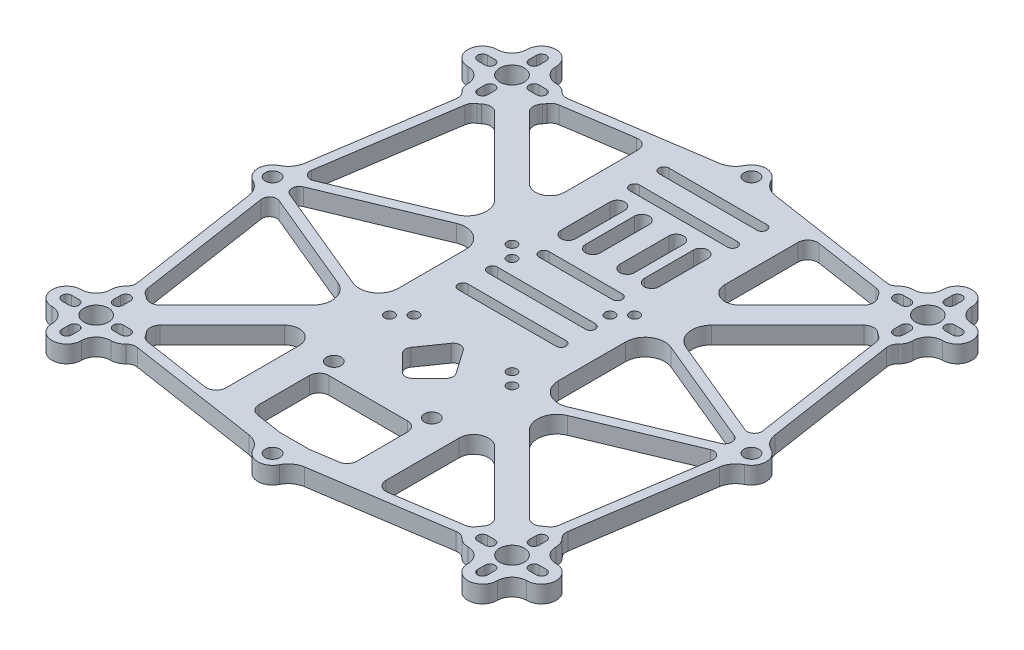
SolidWorks part; units mm, degrees
ref_plane "前视基准面" through (0, 0, 0) normal (0, 0, 1) x (1, 0, 0)
ref_plane "上视基准面" through (0, 0, 0) normal (0, 1, 0) x (1, 0, 0)
ref_plane "右视基准面" through (0, 0, 0) normal (1, 0, 0) x (0, 0, -1)
sketch "草图1" plane through (0, 0, 0) normal (0, 1, 0) x (1, 0, 0)
  line L4 (42.4264, 36.4264) -> (42.4264, 37.9264) construction
  line L5 (41.4264, 36.4264) -> (41.4264, 37.9264)
  line L10 (43.4264, 36.4264) -> (43.4264, 37.9264)
  line L13 (42.4264, 36.4264) -> (42.4264, 37.9264) construction
  line L24 (45.4264, 36.4264) -> (45.4264, 39.4264)
  line L27 (16.3284, 12.8504) -> (16.3284, -12.8504)
  line L28 (48.4264, 42.4264) -> (46.9264, 42.4264) construction
  line L31 (48.4264, 39.4264) -> (45.4264, 39.4264)
  line L33 (48.4264, 45.4264) -> (45.4264, 45.4264)
  line L34 (48.4264, 42.4264) -> (46.9264, 42.4264) construction
  line L35 (48.4264, 43.4264) -> (46.9264, 43.4264)
  line L44 (48.4264, 41.4264) -> (46.9264, 41.4264)
  line L45 (42.4264, 48.4264) -> (42.4264, 46.9264) construction
  line L48 (36.4264, 42.4264) -> (37.9264, 42.4264) construction
  line L51 (45.4264, 48.4264) -> (45.4264, 45.4264)
  line L54 (39.4264, 48.4264) -> (39.4264, 45.4264)
  line L57 (36.4264, 45.4264) -> (39.4264, 45.4264)
  line L59 (42.4264, 48.4264) -> (42.4264, 46.9264) construction
  line L62 (43.4264, 48.4264) -> (43.4264, 46.9264)
  line L63 (41.4264, 48.4264) -> (41.4264, 46.9264)
  line L64 (36.4264, 42.4264) -> (37.9264, 42.4264) construction
  line L65 (36.4264, 41.4264) -> (37.9264, 41.4264)
  line L66 (36.4264, 43.4264) -> (37.9264, 43.4264)
  line L67 (16.3284, 44.3567) -> (33.5024, 41.7553)
  line L68 (0, 42) -> (10, 42)
  line L69 (0, 40) -> (10, 40)
  line L70 (0, 1) -> (0, 5)
  line L71 (0, 1) -> (10, 1)
  line L72 (0, -1) -> (10, -1)
  line L73 (-1, 0) -> (-4.9453, 0)
  line L77 (7.5, 13) -> (0, 13)
  line L78 (48.4035, 2.9662) -> (43.7435, 33.731)
  line L85 (36.4264, -42.4264) -> (37.9264, -42.4264) construction
  line L87 (42.4264, -48.4264) -> (42.4264, -46.9264) construction
  line L88 (48.4264, -42.4264) -> (46.9264, -42.4264) construction
  line L89 (42.4264, -36.4264) -> (42.4264, -37.9264) construction
  line L92 (41.7553, -33.5024) -> (46.4493, -2.5135)
  line L94 (41.7553, 33.5024) -> (46.4493, 2.5135)
  line L95 (16.3284, 19.864) -> (16.3284, 44.3567)
  line L96 (48.4035, -2.9662) -> (43.7435, -33.731)
  line L99 (36.4264, -45.4264) -> (39.4264, -45.4264)
  line L100 (39.4264, -48.4264) -> (39.4264, -45.4264)
  line L101 (45.4264, -48.4264) -> (45.4264, -45.4264)
  line L102 (48.4264, -45.4264) -> (45.4264, -45.4264)
  line L103 (48.4264, -39.4264) -> (45.4264, -39.4264)
  line L104 (45.4264, -36.4264) -> (45.4264, -39.4264)
  line L107 (36.4264, -42.4264) -> (37.9264, -42.4264) construction
  line L108 (36.4264, -41.4264) -> (37.9264, -41.4264)
  line L109 (36.4264, -43.4264) -> (37.9264, -43.4264)
  line L110 (42.4264, -48.4264) -> (42.4264, -46.9264) construction
  line L111 (43.4264, -48.4264) -> (43.4264, -46.9264)
  line L112 (41.4264, -48.4264) -> (41.4264, -46.9264)
  line L113 (48.4264, -42.4264) -> (46.9264, -42.4264) construction
  line L114 (48.4264, -43.4264) -> (46.9264, -43.4264)
  line L115 (48.4264, -41.4264) -> (46.9264, -41.4264)
  line L116 (42.4264, -36.4264) -> (42.4264, -37.9264) construction
  line L117 (41.4264, -36.4264) -> (41.4264, -37.9264)
  line L118 (43.4264, -36.4264) -> (43.4264, -37.9264)
  line L119 (33.731, 43.7435) -> (2.9662, 48.4035)
  line L120 (0, 51.8528) -> (0, 50.3528)
  line L125 (0, 47.3528) -> (0, 42)
  line L126 (0, -47.3528) -> (0, -44.4131)
  line L127 (0, -51.8528) -> (0, -50.3528)
  line L128 (33.731, -43.7435) -> (2.9662, -48.4035)
  line L129 (16.3284, -44.3567) -> (33.5024, -41.7553)
  line L130 (16.3284, -19.864) -> (16.3284, -44.3567)
  line L131 (5.3245, -17.0379) -> (0, -22.3624)
  line L133 (0, -29.3528) -> (10, -29.3528)
  line L135 (10, -43.3528) -> (3, -44.4131)
  line L137 (3, -44.4131) -> (0, -44.4131)
  line L138 (10, -29.3528) -> (10, -43.3528)
  line L139 (0, -29.3528) -> (0, -22.3624)
  line L140 (8.5, 30) -> (8.5, 20) construction
  line L141 (10, 30) -> (10, 20)
  line L142 (7, 30) -> (7, 20)
  line L143 (3.5, 30) -> (3.5, 20) construction
  line L144 (5, 30) -> (5, 20)
  line L145 (2, 30) -> (2, 20)
  line L148 (7.5, 15) -> (0, 15)
  line L149 (0, 7) -> (0, 13)
  line L150 (0, -1) -> (0, -9.4338)
  line L152 (5.3245, -17.0379) -> (0, -9.4338)
  line L154 (0, -9.4338) -> (0, -1)
  line L155 (0, 5) -> (10, 5)
  line L156 (0, 7) -> (10, 7)
  line L157 (0, 15) -> (0, 34)
  line L158 (0, 34) -> (10, 34)
  line L159 (0, 36) -> (10, 36)
  line L160 (0, 36) -> (0, 40)
  line L161 (47.2877, 0) -> (16.3284, -12.8504)
  line L162 (47.2877, 0) -> (16.3284, 12.8504)
  line L163 (39.4674, -35.9319) -> (17.8993, -14.3638)
  line L164 (39.4674, 35.9319) -> (17.8993, 14.3638)
  line L165 (17.8993, 14.3638) -> (46.4493, 2.5135)
  line L166 (16.3284, -19.864) -> (35.9319, -39.4674)
  line L167 (17.8993, -14.3638) -> (46.4493, -2.5135)
  line L168 (16.3284, 19.864) -> (35.9319, 39.4674)
  circle A48 centre (10, 10) radius 1
  circle A49 centre (12.5, 12.5) radius 1
  arc A52 (41.4264, 36.4264) -> (43.4264, 36.4264) centre (42.4264, 36.4264) ccw
  arc A53 (43.4264, 37.9264) -> (41.4264, 37.9264) centre (42.4264, 37.9264) ccw
  arc A54 (39.4674, 35.9319) -> (41.7553, 33.5024) centre (42.4264, 36.4264) ccw
  arc A56 (48.4264, 45.4264) -> (48.4264, 39.4264) centre (48.4264, 42.4264) cw
  arc A57 (48.4264, 43.4264) -> (48.4264, 41.4264) centre (48.4264, 42.4264) cw
  arc A58 (46.9264, 41.4264) -> (46.9264, 43.4264) centre (46.9264, 42.4264) cw
  arc A59 (45.4264, 48.4264) -> (39.4264, 48.4264) centre (42.4264, 48.4264) ccw
  arc A61 (43.4264, 48.4264) -> (41.4264, 48.4264) centre (42.4264, 48.4264) ccw
  arc A62 (41.4264, 46.9264) -> (43.4264, 46.9264) centre (42.4264, 46.9264) ccw
  arc A63 (36.4264, 41.4264) -> (36.4264, 43.4264) centre (36.4264, 42.4264) cw
  arc A64 (37.9264, 43.4264) -> (37.9264, 41.4264) centre (37.9264, 42.4264) cw
  circle A65 centre (42.4264, 42.4264) radius 2.5
  arc A69 (10, 40) -> (10, 42) centre (10, 41) ccw
  arc A71 (10, -1) -> (10, 1) centre (10, 0) ccw
  arc A76 (33.5024, 41.7553) -> (35.9319, 39.4674) centre (36.4264, 42.4264) ccw
  arc A77 (33.5024, -43.0975) -> (36.4264, -45.4264) centre (36.4264, -42.4264) ccw
  arc A79 (0, 50.3528) -> (0, 47.3528) centre (0, 48.8528) cw
  arc A80 (2.9662, 48.4035) -> (0, 51.8528) centre (0, 48.8528) ccw
  circle A81 centre (42.4264, -42.4264) radius 2.5
  arc A82 (35.9319, -39.4674) -> (33.731, -41.1093) centre (36.4264, -42.4264) ccw
  arc A83 (45.4264, -48.4264) -> (39.4264, -48.4264) centre (42.4264, -48.4264) cw
  arc A84 (48.4264, -45.4264) -> (48.4264, -39.4264) centre (48.4264, -42.4264) ccw
  arc A85 (39.4674, -35.9319) -> (41.7553, -33.5024) centre (42.4264, -36.4264) cw
  circle A86 centre (12.5, -12.5) radius 1
  circle A87 centre (10, -10) radius 1
  arc A88 (36.4264, -41.4264) -> (36.4264, -43.4264) centre (36.4264, -42.4264) ccw
  arc A89 (37.9264, -43.4264) -> (37.9264, -41.4264) centre (37.9264, -42.4264) ccw
  arc A90 (43.4264, -48.4264) -> (41.4264, -48.4264) centre (42.4264, -48.4264) cw
  arc A91 (41.4264, -46.9264) -> (43.4264, -46.9264) centre (42.4264, -46.9264) cw
  arc A92 (48.4264, -43.4264) -> (48.4264, -41.4264) centre (48.4264, -42.4264) ccw
  arc A93 (46.9264, -41.4264) -> (46.9264, -43.4264) centre (46.9264, -42.4264) ccw
  arc A94 (41.4264, -36.4264) -> (43.4264, -36.4264) centre (42.4264, -36.4264) cw
  arc A95 (43.4264, -37.9264) -> (41.4264, -37.9264) centre (42.4264, -37.9264) cw
  circle A99 centre (48.8528, 0) radius 1.5
  arc A101 (48.4035, -2.9662) -> (48.4035, 2.9662) centre (48.8528, 0) ccw
  arc A102 (43.7435, 33.731) -> (45.4264, 36.4264) centre (42.4264, 36.4264) ccw
  arc A104 (43.7435, -33.731) -> (45.4264, -36.4264) centre (42.4264, -36.4264) cw
  arc A105 (36.4264, 45.4264) -> (33.731, 43.7435) centre (36.4264, 42.4264) ccw
  arc A106 (2.9662, -48.4035) -> (0, -51.8528) centre (0, -48.8528) cw
  arc A107 (0, -50.3528) -> (0, -47.3528) centre (0, -48.8528) ccw
  arc A108 (33.5024, -41.7553) -> (35.9319, -39.4674) centre (36.4264, -42.4264) cw
  circle A109 centre (10, -26.3528) radius 1.5
  arc A110 (10, 30) -> (7, 30) centre (8.5, 30) ccw
  arc A111 (7, 20) -> (10, 20) centre (8.5, 20) ccw
  arc A112 (5, 30) -> (2, 30) centre (3.5, 30) ccw
  arc A113 (2, 20) -> (5, 20) centre (3.5, 20) ccw
  arc A114 (7.5, 13) -> (7.5, 15) centre (7.5, 14) ccw
  arc A115 (10, 5) -> (10, 7) centre (10, 6) ccw
  arc A116 (10, 34) -> (10, 36) centre (10, 35) ccw
  point P0 (8.5, 25)
  point P11 (42.4264, 37.1764)
  point P16 (42.4264, 37.1764)
  point P28 (47.6764, 42.4264)
  point P29 (47.6764, 42.4264)
  point P44 (5, 30)
  point P47 (42.4264, 47.6764)
  point P48 (37.1764, 42.4264)
  point P49 (42.4264, 47.6764)
  point P54 (37.1764, 42.4264)
  point P63 (5, 0)
  point P118 (15.3284, 0)
  point P127 (37.1764, -42.4264)
  point P134 (42.4264, -47.6764)
  point P139 (47.6764, -42.4264)
  point P144 (42.4264, -37.1764)
  point P145 (42.4264, -37.1764)
  point P166 (3.75, 4)
  point P167 (3.5, 25)
extrude "凸台-拉伸1" add sketch "草图1" along normal blind 3.5 contours A107 L127 A106 L128 A77 L99 L100 A83 L101 L102 A84 L103 L104 A104 L96 A101 L78 A102 L24 L31 A56 L33 L51 A59 L54 L57 A105 L119 A80 L120 A79 L125 L68 A69 L69 L71 A71 L72 L139 L133 L138 L135 L137 L126 A113 L145 A112 region at (43.9876, 0, -35.4516)
fillet "圆角1" radius 2 17 edges at (16.3284, 1.75, -44.3567) (16.3284, 1.75, 44.3567) (41.7553, 1.75, 33.5024) (33.5024, 1.75, 41.7553) (43.7435, 1.75, -33.731) (33.731, 1.75, -43.7435) (33.5024, 1.75, -41.7553) (41.7553, 1.75, -33.5024) (33.731, 1.75, 43.7435) (43.7435, 1.75, 33.731) (10, 1.75, 43.3528) (3, 1.75, 44.4131) (10, 1.75, 29.3528) (35.9319, 1.75, -39.4674) (39.4674, 1.75, -35.9319) (35.9319, 1.75, 39.4674) (39.4674, 1.75, 35.9319)
fillet "圆角2" radius 4 8 edges at (2.9662, 1.75, 48.4035) (2.9662, 1.75, -48.4035) (48.4035, 1.75, -2.9662) (48.4035, 1.75, 2.9662) (16.3284, 1.75, 12.8504) (16.3284, 1.75, -12.8504) (17.8993, 1.75, 14.3638) (17.8993, 1.75, -14.3638)
fillet "圆角3" radius 3 8 edges at (39.4264, 1.75, 45.4264) (45.4264, 1.75, 39.4264) (45.4264, 1.75, 45.4264) (39.4264, 1.75, -45.4264) (45.4264, 1.75, -45.4264) (45.4264, 1.75, -39.4264) (16.3284, 1.75, -19.864) (16.3284, 1.75, 19.864)
mirror "镜向1" about plane through (0, 3.5, 0) normal (-1, 0, 0) of bodies 106
fillet "圆角5" radius 1.5 10 edges at (0, 1.75, 9.4338) (46.4493, 1.75, -2.5135) (46.4493, 1.75, 2.5135) (47.2877, 1.75, 0) (-46.4493, 1.75, -2.5135) (-46.4493, 1.75, 2.5135) (-47.2877, 1.75, 0) (0, 1.75, 22.3624) (-5.3245, 1.75, 17.0379) (5.3245, 1.75, 17.0379)
